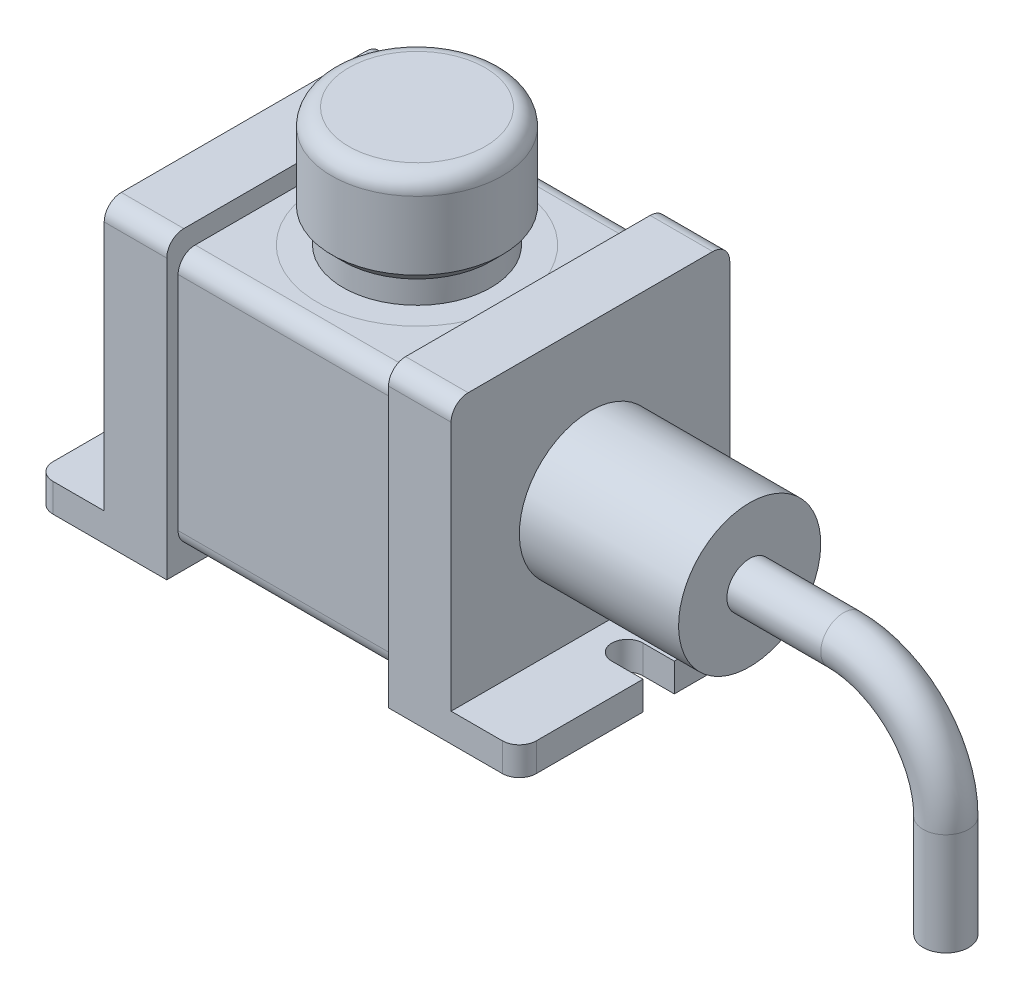
SolidWorks part; units mm, degrees
material "3.1325 (EN-AW 2017A)"
ref_plane "Front Plane" through (0, 0, 0) normal (0, 0, 1) x (1, 0, 0)
ref_plane "Top Plane" through (0, 0, 0) normal (0, 1, 0) x (1, 0, 0)
ref_plane "Right Plane" through (0, 0, 0) normal (1, 0, 0) x (0, 0, -1)
sketch "ｽｹｯﾁ1" plane through (0, 0, 0) normal (0, 0, 1) x (1, 0, 0)
  line L1 (-22.5, -22.5) -> (22.5, -22.5)
  line L2 (-22.5, -22.5) -> (-22.5, 22.5)
  line L3 (-22.5, 22.5) -> (22.5, 22.5)
  line L4 (22.5, -22.5) -> (22.5, 22.5)
  line L5 (-22.5, -22.5) -> (22.5, 22.5) construction
  line L6 (-22.5, 22.5) -> (22.5, -22.5) construction
  point P0 (0, 0)
  dimension "D1" = 45
  dimension "D2" = 45
extrude "ﾎﾞｽ - 押し出し1" add sketch "ｽｹｯﾁ1" along normal mid plane 45
sketch "ｽｹｯﾁ2" plane through (0, 0, 0) normal (0, 0, 1) x (1, 0, 0)
  line L0 (0, 0) -> (0, -30.1748) construction
  line L1 (-19.5, -26) -> (-42.5, -26)
  line L2 (-19.5, -26) -> (-19.5, 26)
  line L3 (-19.5, 26) -> (-30.5, 26)
  line L4 (-42.5, -26) -> (-42.5, -21)
  line L5 (0, 0) -> (-38.5155, 0) construction
  line L6 (-22.5, 22.5) -> (-22.5, -22.5) construction
  line L9 (-42.5, -21) -> (-30.5, -21)
  line L10 (-30.5, 26) -> (-30.5, -21)
  dimension "D1" = 61
  dimension "D2" = 52
  dimension "D3" = 5
  dimension "D4" = 85
  dimension "D5" = 3
extrude "ﾎﾞｽ - 押し出し2" add sketch "ｽｹｯﾁ2" along normal mid plane 49
sketch "ｽｹｯﾁ3" plane through (0, -26, 0) normal (0, -1, 0) x (1, 0, 0)
  line L0 (0, 0) -> (-50.484, 0) construction
  line L1 (-42.5, -2.75) -> (-42.5, 2.75)
  line L2 (-42.5, 24.5) -> (-42.5, -24.5) construction
  line L3 (-42.5, 2.75) -> (-37, 2.75)
  line L4 (-37, -2.75) -> (-42.5, -2.75)
  line L5 (0, 0) -> (0, 29.7807) construction
  arc A0 (-37, 2.75) -> (-37, -2.75) centre (-37, 0) cw
  dimension "D1" = 74
  dimension "D2" = 5.5
extrude "ｶｯﾄ - 押し出し1" cut sketch "ｽｹｯﾁ3" against normal through all both and the other way through all
sketch "ｽｹｯﾁ4" plane through (0, 0, 0) normal (0, 0, 1) x (1, 0, 0)
  line L0 (0, 0) -> (0, 45.839) construction
  line L1 (0, 43.5) -> (-15, 43.5)
  line L2 (-15, 43.5) -> (-15, 28.5)
  line L3 (-15, 28.5) -> (-13, 28.5)
  line L4 (-13, 28.5) -> (-13, 22.5)
  line L5 (22.5, 22.5) -> (-19.5, 22.5) construction
  line L6 (-13, 22.5) -> (0, 22.5)
  line L7 (0, 22.5) -> (0, 43.5)
  dimension "D1" = 21
  dimension "D2" = 30
  dimension "D3" = 6
  dimension "D4" = 26
revolve "回転1" add sketch "ｽｹｯﾁ4" angle 360 about L0
chamfer "面取り1" distance 2 angle 45 1 edges at (0, 28.5, -13)
fillet "ﾌｨﾚｯﾄ1" radius 3 1 edges at (0, 43.5, -15)
mirror "ﾐﾗｰ1" about plane through (0, 0, 0) normal (1, 0, 0) of "ｶｯﾄ - 押し出し1", "ﾎﾞｽ - 押し出し2"
fillet "ﾌｨﾚｯﾄ2" radius 3 12 edges at (42.5, -23.5, -24.5) (42.5, -23.5, 24.5) (25, 26, -24.5) (25, 26, 24.5) (0, 22.5, 22.5) (0, 22.5, -22.5) (-25, 26, -24.5) (-42.5, -23.5, -24.5) (-42.5, -23.5, 24.5) (-25, 26, 24.5) (0, -22.5, -22.5) (0, -22.5, 22.5)
sketch "ｽｹｯﾁ5" plane through (30.5, 0, 0) normal (1, 0, 0) x (0, 0, -1)
  circle A0 centre (0, 0) radius 12.5
  dimension "D1" = 25
extrude "ﾎﾞｽ - 押し出し3" add sketch "ｽｹｯﾁ5" along normal blind 28
sketch "ｽｹｯﾁ6" plane through (58.5, 0, 0) normal (1, 0, 0) x (0, 0, -1)
  circle A0 centre (0, 0) radius 4
  dimension "D1" = 8
sketch "ｽｹｯﾁ9" plane through (0, 0, 0) normal (0, 0, 1) x (1, 0, 0)
  line L0 (58.5, 0) -> (75, 0)
  line L1 (93, -18) -> (93, -36)
  line L6 (37, -21) -> (34.25, -21) construction
  line L11 (37, -21) -> (34.25, -21) construction
  line L12 (39.5, -26) -> (19.5, -26) construction
  arc A0 (75, 0) -> (93, -18) centre (75, -18) cw
  point P4 (0, 0)
  point P5 (75.6439, 0)
  point P9 (0, 0)
  point P10 (0, 0)
  point P11 (60.0464, 1.9795)
  point P15 (93, -30.0263)
  point P16 (93, -19.35)
  point P19 (0, 0)
  dimension "D1" = 8
  dimension "D2" = 56
  dimension "D3" = 10
sweep "ｽｲｰﾌﾟ1" add profiles "ｽｹｯﾁ6" path "ｽｹｯﾁ9"
sketch "ｽｹｯﾁ7" plane through (0, 22.5, 0) normal (0, 1, 0) x (1, 0, 0)
  circle A0 centre (0, 0) radius 17.5
  dimension "D1" = 35
split line "分割ﾗｲﾝ1"
